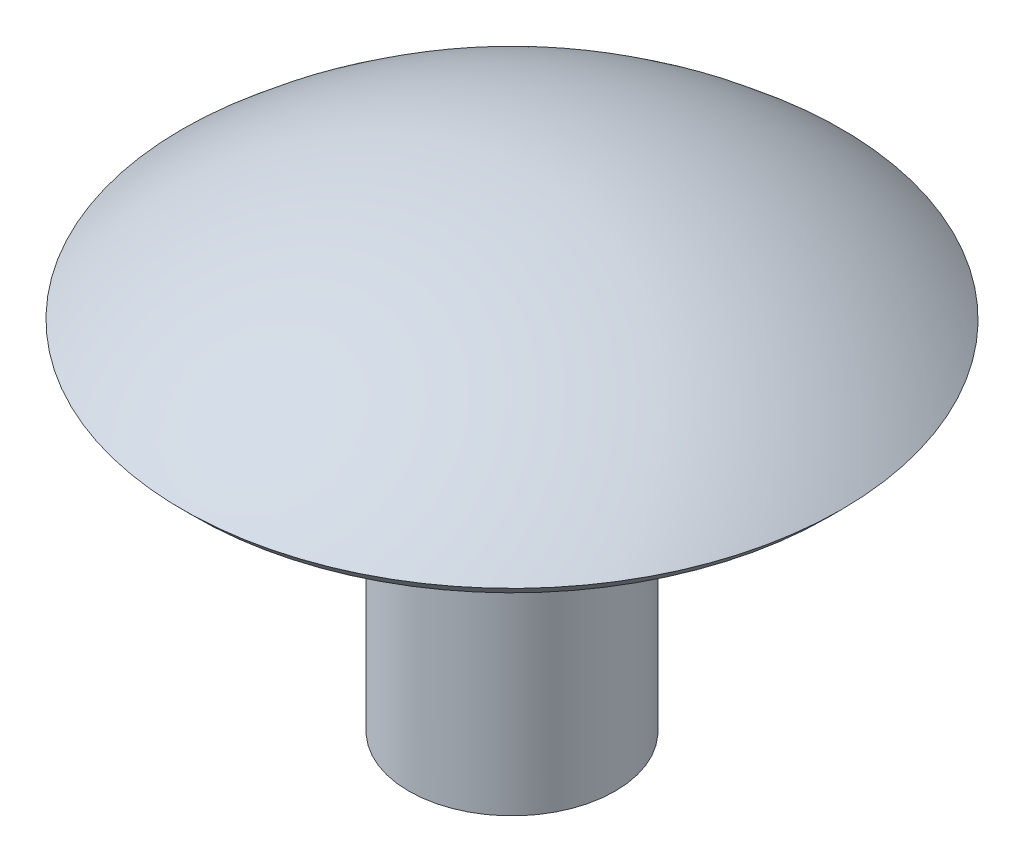
SolidWorks part; units mm, degrees
ref_plane "Front Plane" through (0, 0, 0) normal (0, 0, 1) x (1, 0, 0)
ref_plane "Top Plane" through (0, 0, 0) normal (0, 1, 0) x (1, 0, 0)
ref_plane "Right Plane" through (0, 0, 0) normal (1, 0, 0) x (0, 0, -1)
sketch "Sketch1" plane through (0, 0, 0) normal (0, 1, 0) x (1, 0, 0)
  circle A0 centre (0, 0) radius 1.5
  dimension "D1" = 3
extrude "Boss-Extrude1" add sketch "Sketch1" along normal blind 5
sketch "Sketch2" plane through (0, 5, 0) normal (0, 1, 0) x (1, 0, 0)
  circle A2 centre (0, 0) radius 4.5
  circle A3 centre (0, 0) radius 4.5
  dimension "D1" = 3
extrude "Boss-Extrude2" [suppressed] add sketch "Sketch2" along normal blind 2
fillet "Fillet1" [suppressed] radius 1
sketch "Sketch3" plane through (0, 0, 0) normal (0, 0, 1) x (1, 0, 0)
  line L3 (0, 5) -> (-5, 5)
  line L4 (1.5, 5) -> (-1.5, 5) construction
  line L5 (0, 7) -> (0, 5)
  arc A1 (-5, 5) -> (0, 7) centre (0, -0.25) cw
  dimension "D1" = 5
  dimension "D2" = 2
revolve "Revolve1" add sketch "Sketch3" angle 360 about L5
fillet "Fillet2" radius 0.4 1 edges at (0, 5, 1.5)
chamfer "Chamfer1" distance 0.4 angle 45 1 edges at (-5, 5, 0) first distance on face at (1.9, 5, 0)
